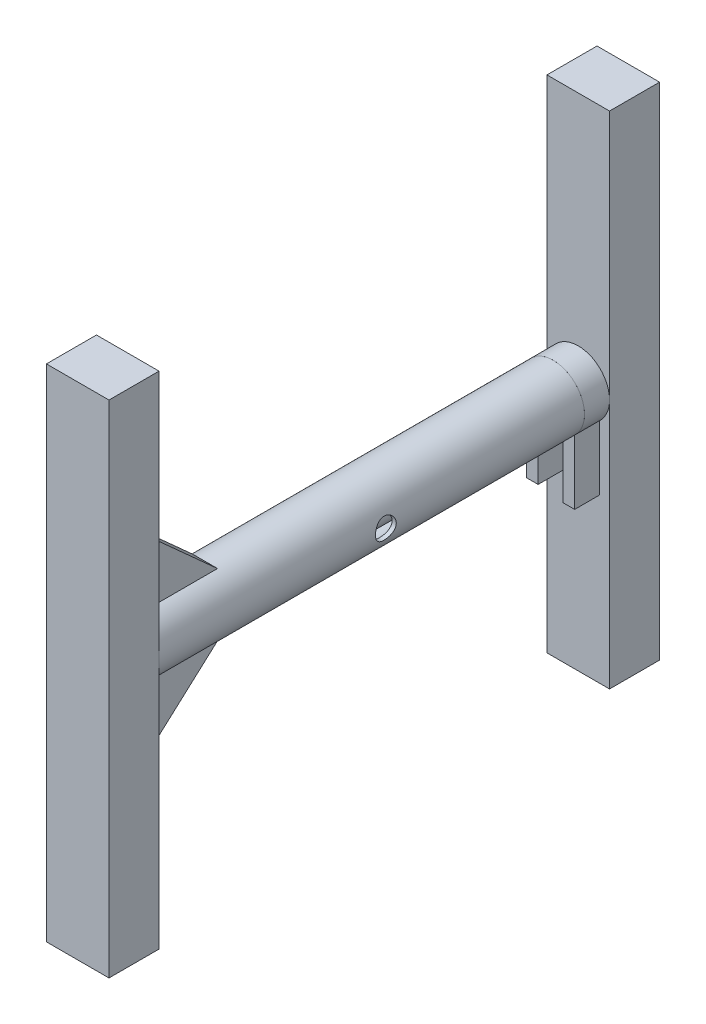
SolidWorks part; units mm, degrees
ref_plane "Front Plane" through (0, 0, 0) normal (0, 0, 1) x (1, 0, 0)
ref_plane "Top Plane" through (0, 0, 0) normal (0, 1, 0) x (1, 0, 0)
ref_plane "Right Plane" through (0, 0, 0) normal (1, 0, 0) x (0, 0, -1)
sketch "Sketch1" plane through (0, 0, 0) normal (0, 0, 1) x (1, 0, 0)
  line L1 (-12.5, 100) -> (12.5, 100)
  line L2 (-12.5, 100) -> (-12.5, -100)
  line L3 (-12.5, -100) -> (12.5, -100)
  line L4 (12.5, 100) -> (12.5, -100)
  line L5 (-12.5, 100) -> (12.5, -100) construction
  line L6 (-12.5, -100) -> (12.5, 100) construction
  point P0 (0, 0)
  dimension "D1" = 25
  dimension "D2" = 200
extrude "Boss-Extrude1" add sketch "Sketch1" along normal blind 20
extrude "Boss-Extrude2" add sketch "Sketch1<2>" along normal blind 20 from offset 200 separate body
sketch "Sketch1<2>" plane through (0, 0, 0) normal (0, 0, 1) x (1, 0, 0) same geometry as "Sketch1"
sketch "Sketch3" plane through (0, 0, 200) normal (0, 0, -1) x (-1, 0, 0)
  circle A0 centre (0, 0) radius 7.5
  dimension "D1" = 15
extrude "Boss-Extrude4" add sketch "Sketch3" along normal up to surface (180 mm away) up to face at (0, 0, 20)
sketch "Sketch4" plane through (0, 0, 200) normal (0, 0, -1) x (-1, 0, 0)
  circle A0 centre (0, 0) radius 12.5
  circle A1 centre (0, 0) radius 10.8479
extrude "Boss-Extrude6" add sketch "Sketch4" along normal blind 170 separate body
sketch "Sketch5" plane through (0, 0, 0) normal (1, 0, 0) x (0, 0, -1)
  circle A0 centre (-109.3668, 0) radius 4.1595
extrude "Cut-Extrude1" cut sketch "Sketch5" along normal blind 206 from offset 8
sketch "Sketch7" [suppressed] plane through (0, 0, 200) normal (0, 0, -1) x (-1, 0, 0)
  circle A0 centre (0, 0) radius 7.5
  dimension "D1" = 15
extrude "Cut-Extrude2" [suppressed] cut sketch "Sketch7" along normal blind 200 from offset 10 offset against normal yes
sketch "Sketch8" [suppressed] plane through (0, 0, 0) normal (1, 0, 0) x (0, 0, -1)
  line L0 (-10, 0) -> (-10, 7.5)
  line L1 (-10, 7.5) -> (-20, 7.5)
  line L2 (-20, -100) -> (-20, 100) construction
  line L3 (-20, 7.5) -> (-20, 20)
  line L4 (-20, 20) -> (-200, 20)
  line L5 (-200, -100) -> (-200, 100) construction
  line L6 (-200, 20) -> (-200, 7.5)
  line L7 (-200, 7.5) -> (-210, 7.5)
  line L8 (-210, 7.5) -> (-210, 0)
  line L9 (-210, 0) -> (-10, 0) construction
  line L10 (-10, 0) -> (-210, 0)
  dimension "D1" = 10
  dimension "D2" = 10
  dimension "D3" = 7.5
  dimension "D4" = 7.5
  dimension "D5" = 20
revolve "Revolve1" [suppressed] add sketch "Sketch8" angle 360 about L9
sketch "Sketch9" plane through (0, 0, 20) normal (0, 0, 1) x (1, 0, 0)
  circle A0 centre (0, 0) radius 12.5
extrude "Boss-Extrude7" add sketch "Sketch9" along normal blind 10 separate body
sketch "Sketch10" plane through (0, 0, 20) normal (0, 0, 1) x (1, 0, 0)
  line L1 (-6.0354, 5.3456) -> (-10.5775, 5.3456)
  line L2 (-6.0354, 5.3456) -> (-6.0354, -33.4954)
  line L3 (-6.0354, -33.4954) -> (-10.5775, -33.4954)
  line L4 (-10.5775, 5.3456) -> (-10.5775, -33.4954)
  line L5 (3.9479, 5.3456) -> (8.5654, 5.3456)
  line L6 (3.9479, 5.3456) -> (3.9479, -34.8184)
  line L7 (3.9479, -34.8184) -> (8.5654, -34.8184)
  line L8 (8.5654, 5.3456) -> (8.5654, -34.8184)
extrude "Boss-Extrude8" add sketch "Sketch10" along normal blind 10 separate body
sketch "Sketch13" plane through (0, 0, 0) normal (1, 0, 0) x (0, 0, -1)
  line L0 (-200, 40.3231) -> (-169.1217, 12.5)
  line L3 (-200, -100) -> (-200, 100) construction
  line L4 (-30, 12.5) -> (-200, 12.5) construction
  line L5 (-169.1217, 12.5) -> (-200, 12.5)
  line L6 (-200, 12.5) -> (-200, 40.3231)
  line L7 (13.75, 0) -> (-13.75, 0) construction
  line L8 (-169.1217, -12.5) -> (-200, -12.5)
  line L9 (-200, -12.5) -> (-200, -40.3231)
  line L10 (-200, -40.3231) -> (-169.1217, -12.5)
extrude "Boss-Extrude10" add sketch "Sketch13" along normal mid plane 10 separate body
ref_plane "Plane1" through (0, 0, 120) normal (0, 0, -1) x (-1, 0, 0)
